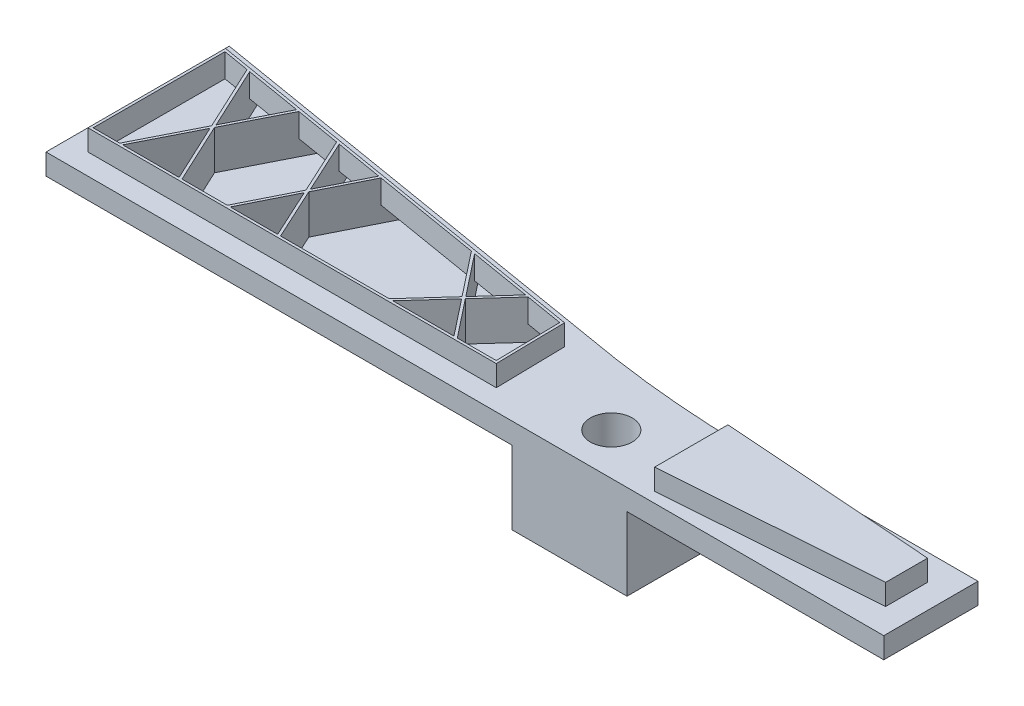
SolidWorks part; units mm, degrees
ref_plane "Front Plane" through (0, 0, 0) normal (0, 0, 1) x (1, 0, 0)
ref_plane "Top Plane" through (0, 0, 0) normal (0, 1, 0) x (1, 0, 0)
ref_plane "Right Plane" through (0, 0, 0) normal (1, 0, 0) x (0, 0, -1)
sketch "Sketch1" plane through (0, 0, 0) normal (0, 1, 0) x (1, 0, 0)
  line L0 (0, 0) -> (0, 17.5)
  line L1 (0, 0) -> (80, 0)
  line L2 (80, 0) -> (80, 9)
  line L3 (80, 9) -> (61, 9)
  line L4 (0, 17.5) -> (41.2073, 10.6074)
  arc A0 (61, 9) -> (41.2073, 10.6074) centre (59.1579, 108.983) cw
extrude "Boss-Extrude1" add sketch "Sketch1" along normal blind 2
sketch "Sketch2" plane through (0, 0, 0) normal (0, -1, 0) x (1, 0, 0)
  line L0 (55.4829, 0) -> (44.4829, 0)
  line L1 (0, 0) -> (80, 0) construction
  line L2 (44.4829, 0) -> (44.4829, -8)
  line L3 (44.4829, -8) -> (55.4829, -8)
  line L4 (55.4829, -8) -> (55.4829, 0)
extrude "Boss-Extrude2" add sketch "Sketch2" along normal blind 7
sketch "Sketch3" plane through (0, -7, 0) normal (0, -1, 0) x (1, 0, 0)
  circle A0 centre (49.9829, -4) radius 2
extrude "Cut-Extrude2" cut sketch "Sketch3" against normal through all
sketch "Sketch4" plane through (0, 2, 0) normal (0, 1, 0) x (1, 0, 0)
  line L6 (40.8773, 8.6348) -> (41, 2)
  line L9 (2, 2) -> (80, 2)
  line L10 (2, 15.1377) -> (2, 2)
  line L11 (40.8773, 8.6348) -> (2, 15.1377)
  line L12 (2, 2) -> (41, 2)
  line L13 (2, 15.1377) -> (2, 2)
  line L14 (40.8773, 8.6348) -> (2, 15.1377)
  dimension "D1" = 2
extrude "Boss-Extrude3" add sketch "Sketch4" along normal blind 2
shell "Shell1" thickness 0.25 removed face at (21.4693, 4, -6.9431)
sketch "Sketch8" plane through (0, 4, 0) normal (0, 1, 0) x (1, 0, 0)
  line L0 (4.9304, 14.3941) -> (10.5962, 2.25)
  line L1 (40.6312, 8.4225) -> (2.25, 14.8424) construction
  line L2 (2.25, 2.25) -> (40.7453, 2.25) construction
  line L3 (10.5962, 13.4463) -> (4.9304, 2.25)
  line L4 (15.2011, 12.6761) -> (20.0112, 2.25)
  line L5 (20.0112, 11.8715) -> (15.2011, 2.25)
  line L6 (30.69, 10.0853) -> (36.8658, 2.25)
  line L7 (36.8658, 9.0523) -> (30.69, 2.25)
rib "Rib2" sketch "Sketch8" sketch "Sketch8" thickness 0.25 extrusion direction normal to sketch draft on no parameters "D1"=0.25
sketch "Sketch9" plane through (0, 2, 0) normal (0, 1, 0) x (1, 0, 0)
  line L0 (77.6813, 6.5019) -> (77.6813, 2.5019)
  line L3 (57.1213, 8.0038) -> (57.1213, 1)
  line L5 (77.6813, 2.5019) -> (57.1213, 1)
  line L6 (57.1213, 8.0038) -> (77.6813, 6.5019)
extrude "Boss-Extrude4" add sketch "Sketch9" along normal blind 2
